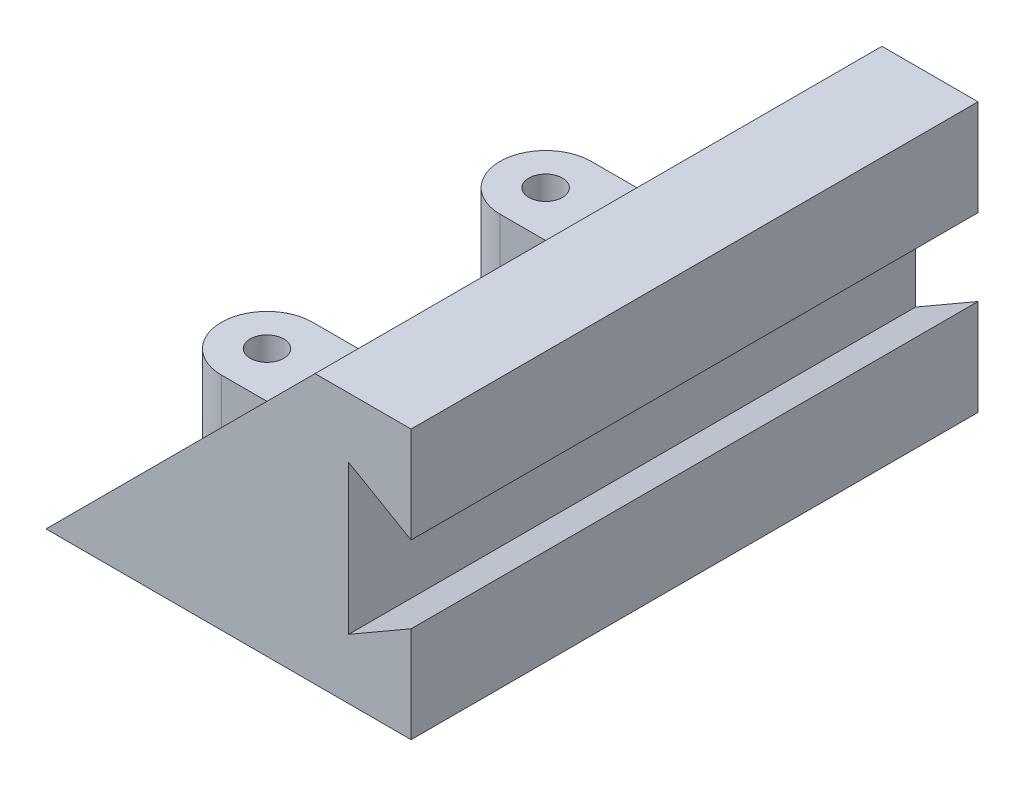
SolidWorks part; units mm, degrees
ref_plane "Front Plane" through (0, 0, 0) normal (0, 0, 1) x (1, 0, 0)
ref_plane "Top Plane" through (0, 0, 0) normal (0, 1, 0) x (1, 0, 0)
ref_plane "Right Plane" through (0, 0, 0) normal (1, 0, 0) x (0, 0, -1)
sketch "Sketch1" plane through (0, 0, 0) normal (0, 0, 1) x (1, 0, 0)
  line L0 (0, 0) -> (0, 8) construction
  line L1 (0, 8) -> (0, 18)
  line L2 (0, 18) -> (-10, 18)
  line L3 (-10, 18) -> (-38, -10)
  line L4 (-38, -10) -> (0, -10)
  line L5 (0, -10) -> (0, 0)
  line L6 (0, 8) -> (-6.5, 11.7528)
  line L7 (-6.5, 11.7528) -> (-6.5, -3.7528)
  line L8 (-6.5, -3.7528) -> (0, 0)
  dimension "D1" = 60
  dimension "D2" = 60
  dimension "D3" = 8
  dimension "D4" = 6.5
  dimension "D5" = 45
  dimension "D6" = 10
  dimension "D7" = 10
  dimension "D8" = 10
extrude "Boss-Extrude1" add sketch "Sketch1" along normal blind 59 contours L3 L4 L5 L8 L7 L6 L1 L2
sketch "Sketch3" plane through (0, -10, 0) normal (0, -1, 0) x (1, 0, 0)
  line L2 (0, 59) -> (0, 0) construction
  line L3 (-25.25, 48.75) -> (-25.25, 39.25)
  line L4 (-25.25, 39.25) -> (-30, 39.25)
  line L5 (-25.25, 48.75) -> (-30, 48.75)
  line L6 (-38, 59) -> (0, 59) construction
  arc A0 (-30, 48.75) -> (-30, 39.25) centre (-30, 44) ccw
  circle A1 centre (-30, 44) radius 1.75
  point P20 (0, 0)
  dimension "D1" = 3.5
  dimension "D2" = 4.75
  dimension "D3" = 4.75
  dimension "D4" = 30
  dimension "D5" = 15
sketch3d "3DSketch2"
  line L0 (-25.25, 2.75, 48.75) -> (-25.25, -10, 48.75) construction
  line L3 (-25.25, -10, 39.25) -> (-25.25, 2.75, 39.25) construction
  point P4 (-25.25, 13.1497, 48.75)
  point P5 (0, 0, 0)
  point P6 (0, 0, 0)
  point P7 (0, 0, 0)
extrude "Boss-Extrude6" add sketch "Sketch3" against normal up to vertex (12.75 mm away) contours L3 L4 A0 L5 up to point (-25.25, 2.75, 48.75)
extrude "Cut-Extrude3" cut sketch "Sketch3<14>" against normal up to surface (12.75 mm away) contours A1 up to face at (-28.8125, 2.75, 44)
sketch "Sketch3<14>" plane through (0, -10, 0) normal (0, -1, 0) x (1, 0, 0) same geometry as "Sketch3"
ref_plane "Plane1" through (0, 0, 29.5) normal (0, 0, 1) x (1, 0, 0)
mirror "Mirror1" about plane through (0, 0, 29.5) normal (0, 0, 1) of "Cut-Extrude3", "Boss-Extrude6"
